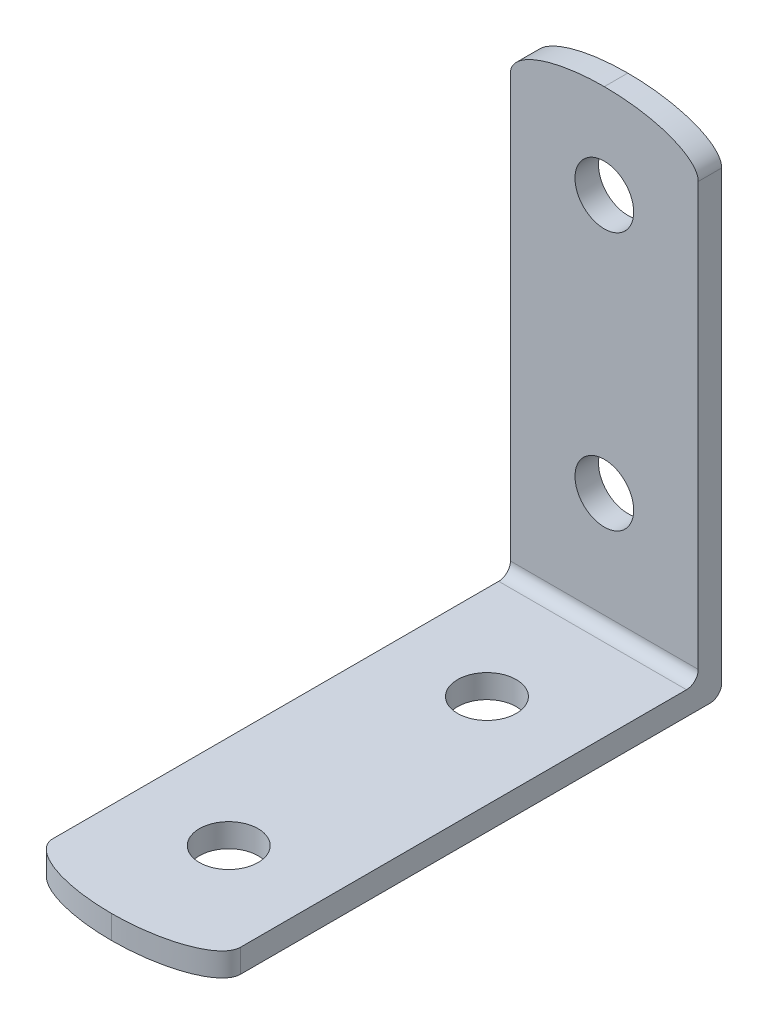
SolidWorks part; units mm, degrees
ref_plane "Plan de face" through (0, 0, 0) normal (0, 0, 1) x (1, 0, 0)
ref_plane "Plan de dessus" through (0, 0, 0) normal (0, 1, 0) x (1, 0, 0)
ref_plane "Plan de droite" through (0, 0, 0) normal (1, 0, 0) x (0, 0, -1)
sketch "Esquisse1" plane through (0, 0, 0) normal (0, 0, 1) x (1, 0, 0)
  line L0 (0, 0) -> (8, 0)
  line L1 (0, 0) -> (-8, 0)
  line L2 (8, 0) -> (8, 42)
  line L3 (8, 42) -> (-8, 42)
  line L4 (-8, 42) -> (-8, 0)
  line L5 (0, 0) -> (0, 12) construction
  line L6 (0, 12) -> (0, 34) construction
  circle A0 centre (0, 12) radius 2.5
  circle A1 centre (0, 34) radius 2.5
  dimension "D1" = 22
  dimension "D2" = 42
  dimension "D3" = 8
  dimension "D4" = 16
  dimension "D5" = 12
extrude "Boss.-Extru.1" add sketch "Esquisse1" along normal blind 2
sketch "Esquisse2" plane through (0, 0, 2) normal (0, 0, 1) x (1, 0, 0)
  line L0 (-8, 0) -> (-8, 2)
  line L1 (-8, 42) -> (-8, 0) construction
  line L2 (-9.6797, 2) -> (8, 2)
  line L3 (8, 0) -> (8, 42) construction
  line L4 (8, 2) -> (8, 0)
  line L5 (8, 0) -> (-8, 0)
  line M3 (-8, 0) -> (8, 0)
  line M4 (8, 0) -> (8, 42)
  line M6 (-8, 42) -> (-8, 0)
  dimension "D1" = 2
extrude "Boss.-Extru.2" add sketch "Esquisse2" along normal blind 42 contours L2 M6 M3 M4 region at (0, 1, 2)
fillet "Congé1" radius 1 2 edges at (0, 0, 0) (0, 2, 2)
sketch "Esquisse3" plane through (0, 0, 0) normal (0, -1, 0) x (1, 0, 0)
  line L0 (0, 0) -> (0, 12) construction
  line L1 (0, 12) -> (0, 34) construction
  circle A0 centre (0, 12) radius 2.5
  circle A1 centre (0, 34) radius 2.5
  dimension "D1" = 12
  dimension "D2" = 22
extrude "Enlèv. mat.-Extru.1" cut sketch "Esquisse3" against normal up to next
fillet "Congé2" radius 3 3 edges at (8, 42, 1) (-8, 1, 44) (8, 1, 44) second distance 8 first distance on face at (8, 11.4482, 11.9482) first distance on face at (-8, 11.4482, 11.9482)
fillet "Congé3" radius 3 1 edges at (-8, 42, 1) second distance 8 first distance on face at (-8, 11.3232, 16.0732)
